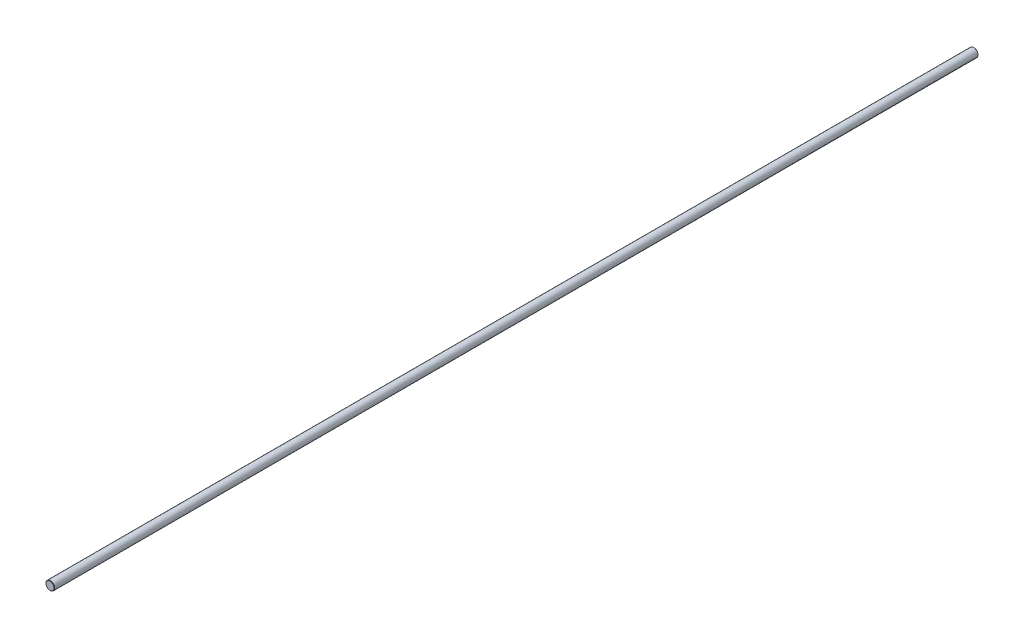
SolidWorks part; units mm, degrees
material "1.0503 (C45)"
ref_plane "Piano frontale" through (0, 0, 0) normal (0, 0, 1) x (1, 0, 0)
ref_plane "Piano superiore" through (0, 0, 0) normal (0, 1, 0) x (1, 0, 0)
ref_plane "Piano destro" through (0, 0, 0) normal (1, 0, 0) x (0, 0, -1)
sketch "Schizzo1" plane through (0, 0, 0) normal (0, 0, 1) x (1, 0, 0)
  circle A0 centre (0, 0) radius 3
  dimension "D1" = 6
extrude "Estrusione-Estrusione1" add sketch "Schizzo1" along normal blind 640
chamfer "Smusso1" distance 0.25 angle 45 2 edges at (3, 0, 0) (3, 0, 640)
